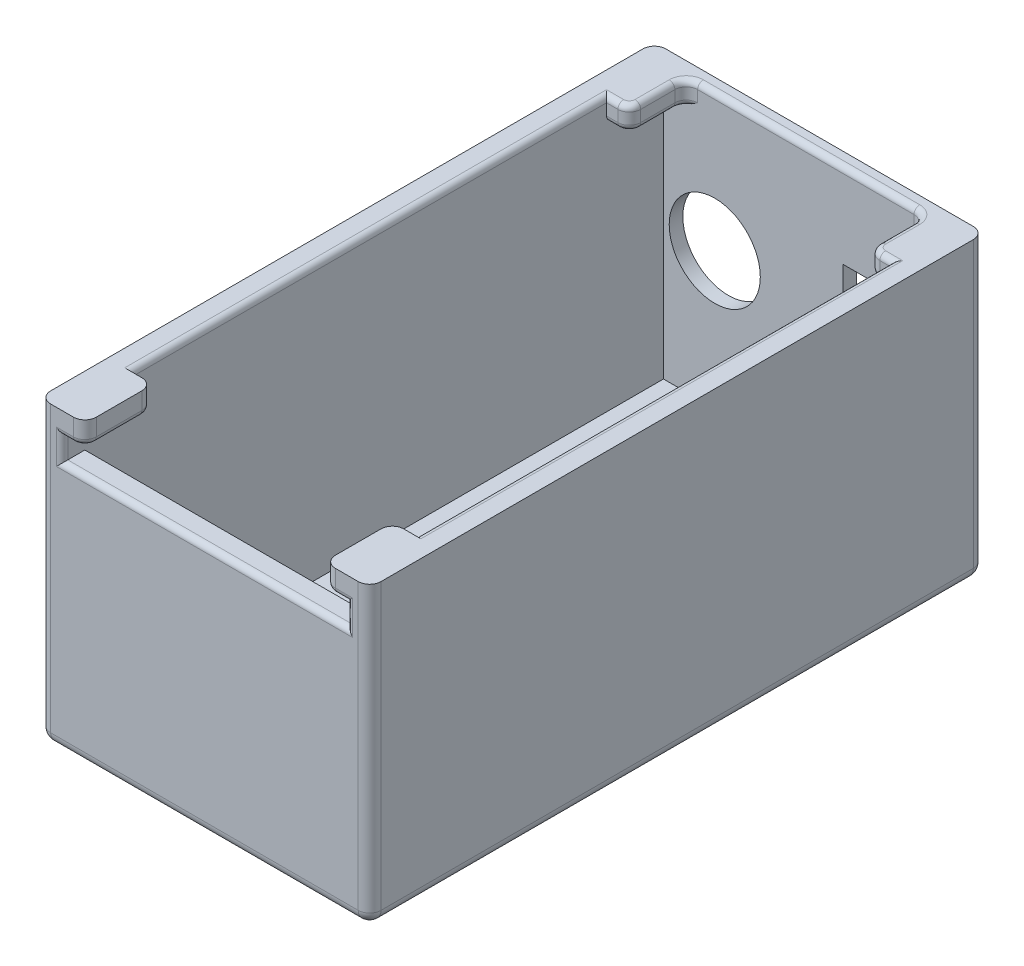
SolidWorks part; units mm, degrees
ref_plane "Front Plane" through (0, 0, 0) normal (0, 0, 1) x (1, 0, 0)
ref_plane "Top Plane" through (0, 0, 0) normal (0, 1, 0) x (1, 0, 0)
ref_plane "Right Plane" through (0, 0, 0) normal (1, 0, 0) x (0, 0, -1)
sketch "Sketch1" plane through (0, 0, 0) normal (0, 1, 0) x (1, 0, 0)
  line L0 (-14.5, -27) -> (-14.5, 27)
  line L1 (-12.5, -25) -> (12.5, -25)
  line L2 (-12.5, -25) -> (-12.5, 25)
  line L3 (-12.5, 25) -> (12.5, 25)
  line L4 (12.5, -25) -> (12.5, 25)
  line L5 (-12.5, -25) -> (12.5, 25) construction
  line L6 (-12.5, 25) -> (12.5, -25) construction
  line L7 (-14.5, 27) -> (14.5, 27)
  line L8 (14.5, -27) -> (14.5, 27)
  line L9 (-14.5, -27) -> (14.5, -27)
  point P0 (0, 0)
  dimension "D1" = 25
  dimension "D2" = 50
  dimension "D3" = 2
extrude "Boss-Extrude1" add sketch "Sketch1" along normal blind 24
sketch "Sketch2" plane through (0, 0, 0) normal (0, -1, 0) x (1, 0, 0)
  line L0 (14.5, -27) -> (-14.5, -27) construction
  line L1 (-14.5, -27) -> (-14.5, 27) construction
  line L2 (-14.5, 27) -> (14.5, 27) construction
  line L3 (14.5, 27) -> (14.5, -27) construction
  line L4 (14.5, -27) -> (-14.5, -27)
  line L5 (-14.5, -27) -> (-14.5, 27)
  line L6 (-14.5, 27) -> (14.5, 27)
  line L7 (14.5, 27) -> (14.5, -27)
extrude "Boss-Extrude2" add sketch "Sketch2" along normal blind 2
sketch "Sketch3" plane through (0, 0, -27) normal (0, 0, -1) x (-1, 0, 0)
  line L0 (-12.5, 24) -> (-12.5, 0) construction
  line L1 (-6.75, 7.4) -> (-3.25, 7.4)
  line L2 (-6.75, 7.4) -> (-6.75, 16.6)
  line L3 (-6.75, 16.6) -> (-3.25, 16.6)
  line L4 (-3.25, 7.4) -> (-3.25, 16.6)
  line L5 (-6.75, 7.4) -> (-3.25, 16.6) construction
  line L6 (-6.75, 16.6) -> (-3.25, 7.4) construction
  line L7 (-12.5, 24) -> (-12.5, 0) construction
  line L8 (12.5, 24) -> (12.5, 0) construction
  line L9 (12.5, 24) -> (12.5, 0) construction
  line L10 (-12.5, 0) -> (12.5, 0) construction
  line L11 (-12.5, 0) -> (12.5, 0) construction
  circle A0 centre (8, 12) radius 4
  point P0 (-5, 12)
  dimension "D5" = 8
  dimension "D1" = 3.5
  dimension "D2" = 9.2
  dimension "D3" = 12
  dimension "D4" = 7.5
  dimension "D6" = 13
  dimension "D7" = 12
extrude "Cut-Extrude1" cut sketch "Sketch3" against normal up to next
sketch "Sketch6" plane through (0, 0, -25) normal (0, 0, 1) x (1, 0, 0)
  line L24 (-12.5, 0) -> (12.5, 0)
  line L25 (12.5, 0) -> (12.5, 24)
  line L26 (12.5, 24) -> (-12.5, 24)
  line L27 (-12.5, 24) -> (-12.5, 0)
  line L28 (-12.5, 0) -> (12.5, 0)
  line L29 (12.5, 0) -> (12.5, 24)
  line L30 (12.5, 24) -> (-12.5, 24)
  line L31 (-12.5, 24) -> (-12.5, 0)
  circle A0 centre (-8, 12) radius 4 construction
  circle A1 centre (-8, 12) radius 4 construction
  dimension "D1" = 0
extrude "Cut-Extrude4" cut sketch "Sketch6" against normal blind 0.8
sketch "Sketch7" plane through (0, 0, 27) normal (0, 0, 1) x (1, 0, 0)
  line L0 (-14.5, 24) -> (14.5, 24) construction
  line L1 (-14.5, 24) -> (14.5, 24) construction
  line L2 (0, 0) -> (0, 24) construction
  line L3 (-12.5, 24) -> (-12.5, 0) construction
  line L4 (-12.5, 24) -> (-12.5, 0) construction
  line L5 (12.5, 0) -> (12.5, 24) construction
  line L6 (-12.5, 22) -> (-10.5, 22)
  line L7 (-10.5, 22) -> (-10.5, 24)
  line L8 (-12.5, 22) -> (-12.5, 20)
  line L9 (-12.5, 20) -> (0, 20)
  line L10 (12.5, 0) -> (12.5, 24) construction
  line L11 (0, 20) -> (12.5, 20)
  line L12 (12.5, 20) -> (12.5, 22)
  line L13 (12.5, 22) -> (10.496, 22)
  line L14 (10.496, 22) -> (10.496, 24)
  line L15 (-10.5, 24) -> (10.496, 24)
  line L16 (-14.5, 24) -> (-14.5, -2) construction
  dimension "D1" = 2
  dimension "D2" = 2
  dimension "D3" = 2
  dimension "D4" = 2
  dimension "D5" = 2.004
  dimension "D6" = 12.5
  dimension "D7" = 2
extrude "Cut-Extrude5" cut sketch "Sketch7" against normal up to surface (52.8 mm away) contours L9 L11 L12 L13 L14 L15 L7 L6 L8 up to face at (0, 12, -25.8)
sketch "Sketch8" plane through (0, 0, -25.8) normal (0, 0, 1) x (1, 0, 0)
  line L0 (-10.5, 22) -> (-10.5, 24) construction
  line L1 (-12.5, 22) -> (-10.5, 22) construction
  line L2 (-14.5, 24) -> (-10.5, 24) construction
  line L3 (-10.5, 22) -> (-10.5, 24)
  line L4 (-12.5, 22) -> (-10.5, 22)
  line L5 (-12.5, 24) -> (-10.5, 24)
  line L9 (10.496, 22) -> (12.5, 22) construction
  line L10 (12.5, 24) -> (12.5, 22) construction
  line L11 (10.496, 24) -> (12.5, 24) construction
  line L12 (-12.5, 22) -> (-12.5, 24)
  line L13 (10.496, 24) -> (10.496, 22) construction
  line L14 (10.496, 22) -> (12.5, 22)
  line L15 (12.5, 24) -> (12.5, 22)
  line L16 (10.496, 24) -> (12.5, 24)
  line L17 (10.496, 24) -> (10.496, 22)
extrude "Boss-Extrude3" add sketch "Sketch8" along normal blind 5 contours L4 L3 L5 L12 | L14 L15 L16 L17
sketch "Sketch9" plane through (0, 0, 25) normal (0, 0, -1) x (-1, 0, 0)
  line L0 (12.5, 24) -> (10.5, 24) construction
  line L1 (12.5, 24) -> (12.5, 22) construction
  line L2 (10.5, 24) -> (10.5, 22) construction
  line L3 (10.5, 22) -> (12.5, 22) construction
  line L4 (12.5, 24) -> (10.5, 24)
  line L5 (10.5, 24) -> (10.5, 22)
  line L6 (10.5, 22) -> (12.5, 22)
  line L7 (12.5, 24) -> (12.5, 22)
  line L8 (-10.496, 24) -> (-10.496, 22) construction
  line L9 (-10.496, 22) -> (-12.5, 22) construction
  line L10 (-12.5, 24) -> (-12.5, 22) construction
  line L11 (-10.496, 24) -> (-12.5, 24) construction
  line L12 (-10.496, 24) -> (-10.496, 22)
  line L13 (-10.496, 22) -> (-12.5, 22)
  line L14 (-12.5, 24) -> (-12.5, 22)
  line L15 (-10.496, 24) -> (-12.5, 24)
extrude "Boss-Extrude4" add sketch "Sketch9" along normal blind 4
fillet "Fillet3" radius 1 16 edges at (0, -2, -27) (-14.5, -2, 0) (0, -2, 27) (14.5, -2, 0) (-10.5, 23, 21) (10.496, 23, -20.8) (-10.5, 23, -20.8) (10.496, 23, 21) (-14.5, 11, -27) (14.5, 11, -27) (-14.5, 11, 27) (14.5, 11, 27) (-10.5, 23, 27) (10.496, 23, 27) (-10.5, 23, -25.8) (10.496, 23, -25.8)
fillet "Fillet5" radius 0.5 32 edges at (-12, 24, -20.8) (11.998, 24, -20.8) (10.7889, 24, -21.0929) (10.496, 24, -23.3) (10.2031, 24, -25.5071) (-0.002, 24, -25.8) (-10.2071, 24, -25.5071) (-10.5, 24, -23.3) (-10.2071, 22, -25.5071) (-10.5, 22, -23.3) (-12, 22, -20.8) (11.998, 22, -20.8) (10.2031, 22, -25.5071) (10.496, 22, -23.3) (11.998, 22, 21) (10.7889, 22, 21.2929) (10.496, 22, 24) (10.7889, 22, 26.7071) (-12, 22, 21) (-10.7929, 22, 21.2929) (-10.5, 22, 24) (-10.7929, 22, 26.7071) (12.5, 24, 0.1) (-12.5, 24, 0.1) (-10.7929, 24, -21.0929) (-10.7929, 22, -21.0929) (10.7889, 22, -21.0929) (11.998, 22, 27) (12.5, 21, 27) (-12, 22, 27) (-12.5, 21, 27) (0, 20, 27)
